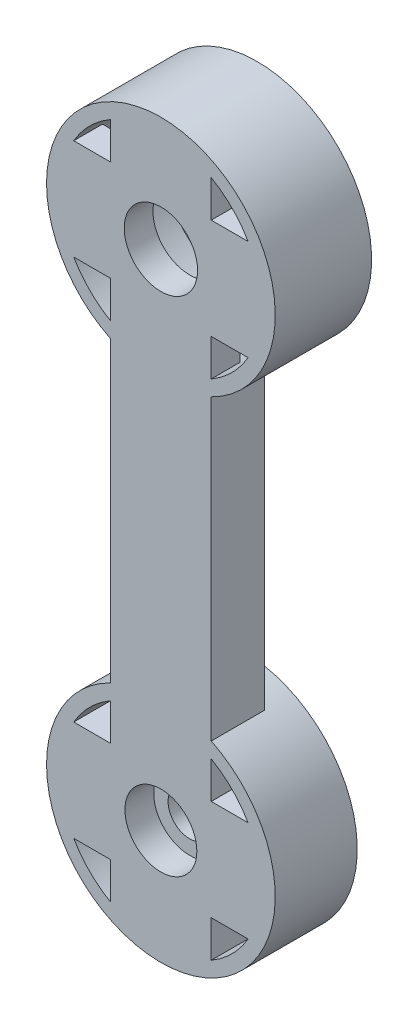
SolidWorks part; units mm, degrees
ref_plane "Front Plane" through (0, 0, 0) normal (0, 0, 1) x (1, 0, 0)
ref_plane "Top Plane" through (0, 0, 0) normal (0, 1, 0) x (1, 0, 0)
ref_plane "Right Plane" through (0, 0, 0) normal (1, 0, 0) x (0, 0, -1)
sketch "Sketch1" plane through (0, 0, 0) normal (0, 0, 1) x (1, 0, 0)
  line L5 (0, -17.5) -> (12.7696, -17.5) construction
  line L26 (0, 0) -> (0, -35) construction
  line L32 (0, 3.5) -> (7.1381, 3.5)
  line L33 (7.1381, 3.5) -> (-7.1381, 3.5)
  line L34 (0, -3.5) -> (7.1381, -3.5)
  line L35 (7.1381, -3.5) -> (-7.1381, -3.5)
  line L36 (3.5, -35) -> (3.5, -41.0622)
  line L37 (-3.5, -35) -> (-3.5, -41.0622)
  line L38 (-3.5, 0) -> (-3.5, 6.0622)
  line L45 (-3.5, 0) -> (-3.5, -35)
  line L47 (3.5, 0) -> (3.5, -35)
  line L48 (3.5, 0) -> (3.5, 6.0622)
  line L49 (7.1381, -31.5) -> (-7.1381, -31.5)
  line L50 (0, -31.5) -> (7.1381, -31.5)
  line L51 (7.1381, -38.5) -> (-7.1381, -38.5)
  line L52 (0, -38.5) -> (7.1381, -38.5)
  circle A0 centre (0, 0) radius 7.95
  circle A1 centre (0, 0) radius 3.5
  circle A2 centre (0, 0) radius 7
  circle A6 centre (0, 0) radius 1.5
  circle A11 centre (0, -35) radius 1.5
  circle A12 centre (0, -35) radius 7
  circle A13 centre (0, -35) radius 3.5
  circle A14 centre (0, -35) radius 7.95
  point P20 (0, -35)
  point P34 (0, -35)
  point P42 (0, 0)
  dimension "D1" = 15.9
  dimension "D2" = 7
  dimension "D6" = 14
  dimension "D9" = 3
  dimension "D3" = 7
  dimension "D7" = 35
extrude "Boss-Extrude4" add sketch "Sketch1" along normal blind 3 contours L48 A2 L38 L33 L32 | A2 L32 A0 L33 | L45 A14 L47 A0 | A14 L51 A12 | A12 L36 L51 L37 | A14 L49 A12 L51 | L36 A13 L51 | L51 A13 L37 | A14 L51 A12 L49 | A13 A11 | L45 A13 L49 | L49 A13 L47 | A12 L45 L49 L47 | A14 L49 A12 L45 | A14 L47 A12 L49 | A14 L45 A12 L47 | A12 L51 L37 L45 L49 | A12 L50 L47 L36 L52 | L45 A2 L47 L34 L35 | A2 L45 A0 L47 | A2 L47 A0 L34 | A2 L34 A0 L32 | A2 L33 A0 L35 | A2 L35 A0 L45 | L33 A2 L35 L45 L38 | L35 A2 L33 L48 L47 | A1 L34 L47 | A1 A6 | A1 L45 L35 | A1 L33 L38 | A1 L48 L32 region at (0, 5.1101, 0) region at (-2.7182, 2.7182, 0) region at (2.7182, 2.7182, 0) region at (2.4049, 2.4049, 0) region at (5.1101, 0, 0) region at (-5.1101, 0, 0) region at (2.7182, -2.7182, 0) region at (-2.7182, -2.7182, 0) region at (5.0555, 5.0555, 0) region at (7.1812, 0, 0) region at (-7.1812, 0, 0) region at (0, -5.1101, 0) region at (-5.2259, -5.2259, 0) region at (5.2259, -5.2259, 0) region at (0, -7.1812, 0) region at (0, -17.5, 0) region at (5.2259, -29.7741, 0) region at (0, -27.8188, 0) region at (-5.2259, -29.7741, 0) region at (0, -29.8899, 0) region at (7.1812, -35, 0) region at (-7.1812, -35, 0) region at (5.1101, -35, 0) region at (2.7182, -32.2818, 0) region at (-2.7182, -32.2818, 0) region at (-5.1101, -35, 0) region at (-6.6001, -38.6495, 0) region at (2.4049, -37.4049, 0) region at (2.7182, -37.7182, 0) region at (-2.7182, -37.7182, 0) region at (0, -40.1101, 0)
sketch "Sketch3" plane through (0, 0, 0) normal (0, 0, -1) x (-1, 0, 0)
  line L0 (-3.5, 6.0622) -> (-3.5, 3.5)
  line L1 (-3.5, 3.5) -> (-6.0622, 3.5)
  line L2 (-3.5, -6.0622) -> (-3.5, -3.5)
  line L3 (-3.5, -3.5) -> (-6.0622, -3.5)
  line L4 (3.5, -6.0622) -> (3.5, -3.5)
  line L5 (3.5, -3.5) -> (6.0622, -3.5)
  line L6 (3.5, 6.0622) -> (3.5, 3.5)
  line L7 (3.5, 3.5) -> (6.0622, 3.5)
  line L8 (0, 0) -> (0, -35) construction
  line L9 (0, -35) -> (0, -17.5) construction
  line L10 (0, -17.5) -> (14.5774, -17.5) construction
  line L11 (-3.5, 3.5) -> (-6.0622, 3.5)
  line L12 (-3.5, 6.0622) -> (-3.5, 3.5)
  line L13 (-3.5, -3.5) -> (-6.0622, -3.5)
  line L14 (-3.5, -6.0622) -> (-3.5, -3.5)
  line L15 (3.5, -3.5) -> (6.0622, -3.5)
  line L16 (3.5, -6.0622) -> (3.5, -3.5)
  line L17 (3.5, 3.5) -> (6.0622, 3.5)
  line L18 (3.5, 6.0622) -> (3.5, 3.5)
  line L19 (3.5, -41.0622) -> (3.5, -38.5)
  line L20 (3.5, -38.5) -> (6.0622, -38.5)
  line L21 (3.5, -28.9378) -> (3.5, -31.5)
  line L22 (3.5, -31.5) -> (6.0622, -31.5)
  line L23 (-3.5, -28.9378) -> (-3.5, -31.5)
  line L24 (-3.5, -31.5) -> (-6.0622, -31.5)
  line L25 (-3.5, -41.0622) -> (-3.5, -38.5)
  line L26 (-3.5, -38.5) -> (-6.0622, -38.5)
  line L27 (3.5, -38.5) -> (6.0622, -38.5)
  line L28 (3.5, -41.0622) -> (3.5, -38.5)
  line L29 (3.5, -31.5) -> (6.0622, -31.5)
  line L30 (3.5, -28.9378) -> (3.5, -31.5)
  line L31 (-3.5, -31.5) -> (-6.0622, -31.5)
  line L32 (-3.5, -28.9378) -> (-3.5, -31.5)
  line L33 (-3.5, -38.5) -> (-6.0622, -38.5)
  line L34 (-3.5, -41.0622) -> (-3.5, -38.5)
  circle A0 centre (0, 0) radius 1.5
  circle A1 centre (0, 0) radius 7.95
  circle A2 centre (0, 0) radius 7
  circle A3 centre (0, -35) radius 7
  circle A4 centre (0, -35) radius 7.95
  circle A5 centre (0, -35) radius 1.5
  line M2 (3.5, -38.5) -> (6.0622, -38.5)
  arc M3 (6.0622, -38.5) -> (3.5, -41.0622) centre (0, -35) cw
  line M4 (3.5, -41.0622) -> (3.5, -38.5)
  line M5 (-3.5, -38.5) -> (-3.5, -41.0622)
  arc M6 (-3.5, -41.0622) -> (-6.0622, -38.5) centre (0, -35) cw
  line M7 (-6.0622, -38.5) -> (-3.5, -38.5)
  arc M9 (3.5, -7.1381) -> (-3.5, -7.1381) centre (0, 0) ccw
  arc M11 (-3.5, -27.8619) -> (3.5, -27.8619) centre (0, -35) ccw
  line M12 (6.0622, -31.5) -> (3.5, -31.5)
  line M13 (3.5, -31.5) -> (3.5, -28.9378)
  arc M14 (3.5, -28.9378) -> (6.0622, -31.5) centre (0, -35) cw
  arc M15 (-3.5, -6.0622) -> (-6.0622, -3.5) centre (0, 0) cw
  line M16 (-6.0622, -3.5) -> (-3.5, -3.5)
  line M17 (-3.5, -3.5) -> (-3.5, -6.0622)
  line M18 (-3.5, -31.5) -> (-6.0622, -31.5)
  arc M19 (-6.0622, -31.5) -> (-3.5, -28.9378) centre (0, -35) cw
  line M20 (-3.5, -28.9378) -> (-3.5, -31.5)
  line M21 (3.5, -3.5) -> (6.0622, -3.5)
  arc M22 (6.0622, -3.5) -> (3.5, -6.0622) centre (0, 0) cw
  line M23 (3.5, -6.0622) -> (3.5, -3.5)
  line M24 (6.0622, 3.5) -> (3.5, 3.5)
  line M25 (3.5, 3.5) -> (3.5, 6.0622)
  arc M26 (3.5, 6.0622) -> (6.0622, 3.5) centre (0, 0) cw
  arc M27 (-6.0622, 3.5) -> (-3.5, 6.0622) centre (0, 0) cw
  line M28 (-3.5, 6.0622) -> (-3.5, 3.5)
  line M29 (-3.5, 3.5) -> (-6.0622, 3.5)
  circle M30 centre (0, 0) radius 1.5
  circle M31 centre (0, -35) radius 1.5
  dimension "D1" = 15.9
extrude "Boss-Extrude5" add sketch "Sketch3" along normal blind 3 contours A1 A2 M9 M26 M22 M15 M27 | A2 M25 M28 M29 M16 M17 M23 M21 M24 M30 | A3 M4 M2 M12 M13 M20 M18 M7 M5 M31 | A4 A3 M11 M3 M6 M19 M14 region at (0, 6.802, 0) region at (0, -41.802, 0) region at (-6.5556, -4.0868, 0) region at (4.0868, -41.5556, 0)
sketch "Sketch4" plane through (0, 0, 3) normal (0, 0, 1) x (1, 0, 0)
  line L0 (0, 0) -> (0, -35) construction
  line L1 (0, -35) -> (0, 0) construction
  line L2 (0, -17.5) -> (19.6941, -17.5) construction
  circle A1 centre (0, -35) radius 2.5
  circle A2 centre (0, 0) radius 2.5
  dimension "D2" = 5
extrude "Cut-Extrude1" cut sketch "Sketch4" against normal blind 1.5
sketch "Sketch5" plane through (0, 0, -3) normal (0, 0, -1) x (-1, 0, 0)
  circle A0 centre (0, 0) radius 7
extrude "Cut-Extrude2" cut sketch "Sketch5" against normal blind 4
sketch "Sketch6" plane through (0, 0, -3) normal (0, 0, -1) x (-1, 0, 0)
  circle A0 centre (0, -35) radius 7.95
extrude "Cut-Extrude3" cut sketch "Sketch6" against normal blind 1
sketch "Sketch7" plane through (0, 0, 1.5) normal (0, 0, 1) x (1, 0, 0)
  circle A0 centre (0, -35) radius 2.5
extrude "Cut-Extrude4" cut sketch "Sketch7" against normal blind 0.5
sketch "Sketch8" plane through (0, 0, -3) normal (0, 0, -1) x (-1, 0, 0)
  circle A0 centre (0, 0) radius 7.95
  circle A1 centre (0, 0) radius 7
extrude "Boss-Extrude6" add sketch "Sketch8" along normal blind 0.7
sketch "Sketch9" plane through (0, 0, -2) normal (0, 0, -1) x (-1, 0, 0)
  line L0 (-3.5, -28.9378) -> (-3.5, -31.5)
  line L1 (-3.5, -31.5) -> (-6.0622, -31.5)
  line L2 (-6.0622, -38.5) -> (-3.5, -38.5)
  line L3 (-3.5, -38.5) -> (-3.5, -41.0622)
  line L4 (6.0622, -38.5) -> (3.5, -38.5)
  line L5 (3.5, -38.5) -> (3.5, -41.0622)
  line L6 (3.5, -28.9378) -> (3.5, -31.5)
  line L7 (3.5, -31.5) -> (6.0622, -31.5)
  circle A0 centre (0, -35) radius 7.95
  circle A1 centre (0, -35) radius 7
  circle A2 centre (0, -35) radius 1.5
  line M1 (6.0622, -31.5) -> (3.5, -31.5)
  line M2 (3.5, -31.5) -> (3.5, -28.9378)
  arc M3 (3.5, -28.9378) -> (6.0622, -31.5) centre (0, -35) cw
  arc M4 (-3.5, -41.0622) -> (-6.0622, -38.5) centre (0, -35) cw
  line M5 (-6.0622, -38.5) -> (-3.5, -38.5)
  line M6 (-3.5, -38.5) -> (-3.5, -41.0622)
  arc M7 (6.0622, -38.5) -> (3.5, -41.0622) centre (0, -35) cw
  line M8 (3.5, -41.0622) -> (3.5, -38.5)
  line M9 (3.5, -38.5) -> (6.0622, -38.5)
  circle M10 centre (0, -35) radius 7.95
  line M11 (-3.5, -31.5) -> (-6.0622, -31.5)
  arc M12 (-6.0622, -31.5) -> (-3.5, -28.9378) centre (0, -35) cw
  line M13 (-3.5, -28.9378) -> (-3.5, -31.5)
  circle M14 centre (0, -35) radius 1.5
extrude "Boss-Extrude8" add sketch "Sketch9" along normal blind 0.7 contours A1 M2 M13 M11 M5 M6 M8 M9 M1 M14 | A1 M10 M3 M7 M4 M12 region at (0, -28.198, -2) region at (7.7251, -35, -2)
sketch "Sketch10" plane through (0, 0, 0) normal (0, 0, -1) x (-1, 0, 0)
  line L2 (-3.5, -7.1381) -> (-3.5, -27.8619)
  line L4 (3.5, -7.1381) -> (3.5, -27.8619)
  circle A0 centre (0, 0) radius 7.95
  circle A1 centre (0, -35) radius 7.95
  line M1 (-3.5, -7.1381) -> (-3.5, -27.8619)
  arc M2 (-3.5, -27.8619) -> (3.5, -27.8619) centre (0, -35) cw
  line M3 (3.5, -27.8619) -> (3.5, -7.1381)
  arc M4 (3.5, -7.1381) -> (-3.5, -7.1381) centre (0, 0) cw
extrude "Boss-Extrude9" add sketch "Sketch10" along normal blind 0.7 contours M4 M1 M2 M3 region at (0, -17.5, 0)
sketch "Sketch11" plane through (0, 0, 3) normal (0, 0, 1) x (1, 0, 0)
  circle A0 centre (0, 0) radius 2.55
  dimension "D1" = 5.1
extrude "Cut-Extrude5" cut sketch "Sketch11" against normal through all
